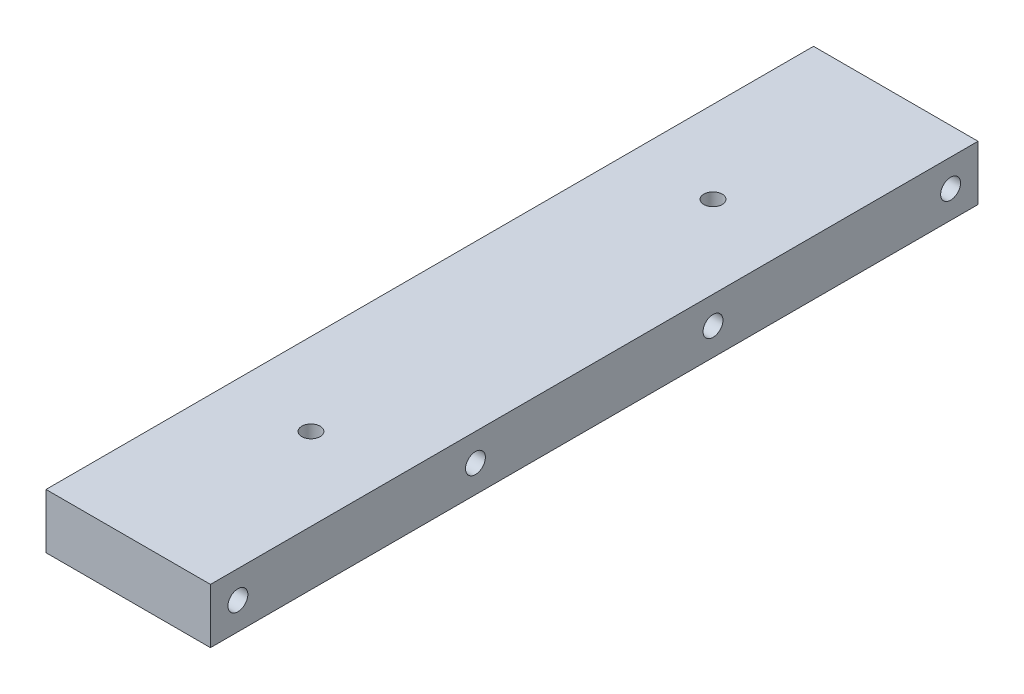
SolidWorks part; units mm, degrees
ref_plane "Front Plane" through (0, 0, 0) normal (0, 0, 1) x (1, 0, 0)
ref_plane "Top Plane" through (0, 0, 0) normal (0, 1, 0) x (1, 0, 0)
ref_plane "Right Plane" through (0, 0, 0) normal (1, 0, 0) x (0, 0, -1)
sketch "Sketch2" plane through (0, 0, 0) normal (0, 1, 0) x (1, 0, 0)
  line L0 (0, 0) -> (28.575, 0)
  line L1 (28.575, 0) -> (28.575, 133.35)
  line L2 (28.575, 133.35) -> (0, 133.35)
  line L3 (0, 133.35) -> (0, 0)
  dimension "D1" = 133.35
  dimension "D2" = 28.575
extrude "Boss-Extrude1" add sketch "Sketch2" along normal blind 9.525
sketch "Sketch3" plane through (28.575, 0, 0) normal (1, 0, 0) x (0, 0, -1)
  line L0 (0, 9.525) -> (0, 0) construction
  line L1 (0, 9.525) -> (133.35, 9.525) construction
  point P0 (4.7625, 4.7625)
  dimension "D1" = 4.7625
  dimension "D2" = 4.7625
sketch "Sketch4" plane through (28.575, 0, 0) normal (1, 0, 0) x (0, 0, -1)
  point P0 (4.7625, 4.7625)
hole_wizard "#5 Clearance Hole1" positions "Sketch4" profile "Sketch5" hole size "#5" standard "ANSI Inch"
sketch "Sketch5" plane through (28.575, 4.7625, -4.7625) normal (0, 1, 0) x (0, 0, -1)
  line L0 (0, 0) -> (0, 13.7378)
  line L1 (0, 13.7378) -> (1.7272, 12.7)
  line L2 (1.7272, 12.7) -> (1.7272, 0)
  line L5 (1.7272, 0) -> (0, 0)
  line L10 (0, 13.7378) -> (-1.7272, 12.7) construction
  line L11 (0, -6.35) -> (0, 107.95) construction
  dimension "Hole Dia." = 3.4544
  dimension "Hole Depth" = 12.7
  dimension "Drill Angle" = 118
pattern_linear "LPattern1" count 4 spacing 41.275 along (0, 0, -1) of "#5 Clearance Hole1"
sketch "Sketch6" plane through (0, 0, 0) normal (-1, 0, 0) x (0, 0, 1)
  line L0 (-133.35, 9.525) -> (-133.35, 0) construction
  line L1 (-133.35, 9.525) -> (0, 9.525) construction
  point P0 (-128.5875, 4.7625)
  dimension "D1" = 4.7625
  dimension "D2" = 4.7625
hole_wizard "#5 Clearance Hole2" positions "Sketch6" profile "Sketch7" hole size "#5" standard "ANSI Inch"
sketch "Sketch7" plane through (0, 4.7625, -128.5875) normal (0, 1, 0) x (0, 0, 1)
  line L0 (0, 0) -> (0, 13.7378)
  line L1 (0, 13.7378) -> (1.7272, 12.7)
  line L2 (1.7272, 12.7) -> (1.7272, 0)
  line L5 (1.7272, 0) -> (0, 0)
  line L10 (0, 13.7378) -> (-1.7272, 12.7) construction
  line L11 (0, -6.35) -> (0, 107.95) construction
  dimension "Hole Dia." = 3.4544
  dimension "Hole Depth" = 12.7
  dimension "Drill Angle" = 118
pattern_linear "LPattern2" count 4 spacing 41.275 along (0, 0, 1) of "#5 Clearance Hole2"
sketch "Sketch8" plane through (0, 0, 0) normal (0, -1, 0) x (1, 0, 0)
  line L0 (0, 0) -> (14.2875, 0)
  line L1 (0, 0) -> (28.575, 0) construction
  line L2 (28.575, -133.35) -> (0, -133.35) construction
  line L3 (0, -133.35) -> (0, 0) construction
  circle A0 centre (14.2875, -31.75) radius 1.5875
  circle A1 centre (14.2875, -101.6) radius 1.5875
  point P5 (14.2875, -31.75)
  point P6 (14.2875, -101.6)
  point P15 (0, 0)
  dimension "D5" = 3.175
  dimension "D6" = 3.175
  dimension "D1" = 31.75
  dimension "D2" = 31.75
  dimension "D3" = 14.2875
  dimension "D4" = 14.2875
extrude "Cut-Extrude2" cut sketch "Sketch8" against normal through all contours A0 | A1 region at (14.2875, 0, -31.75) region at (14.2875, 0, -101.6)
